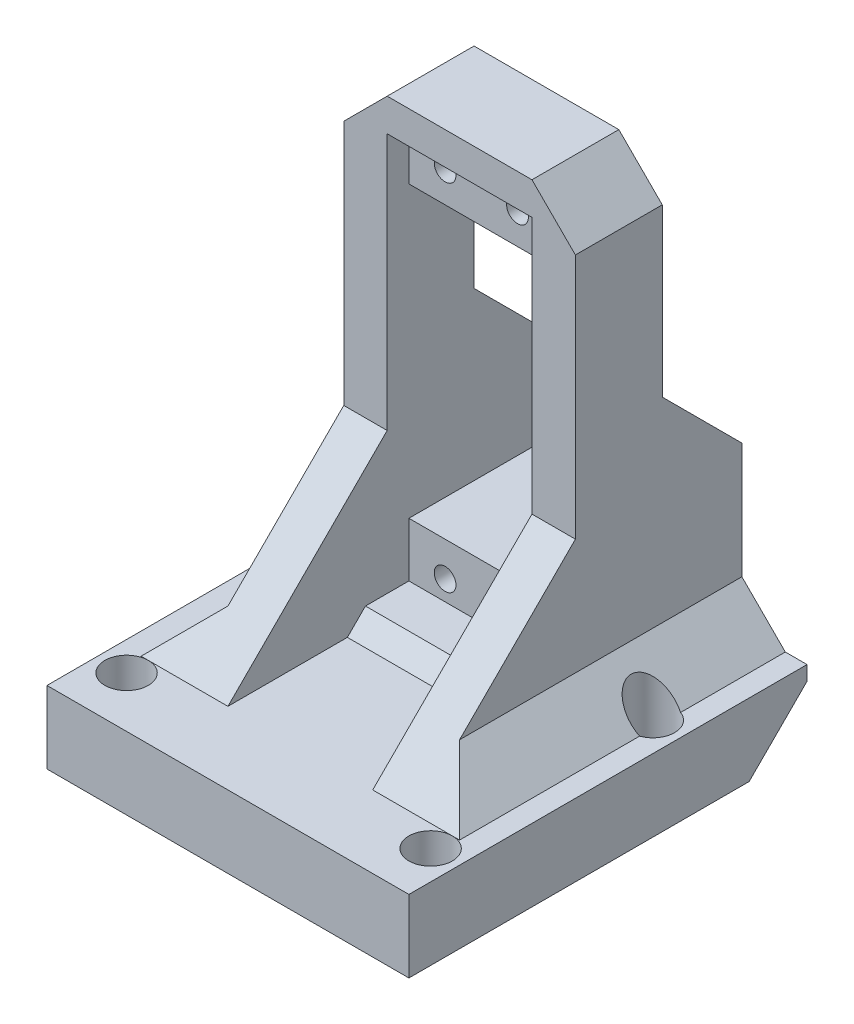
SolidWorks part; units mm, degrees
ref_plane "Front Plane" through (0, 0, 0) normal (0, 0, 1) x (1, 0, 0)
ref_plane "Top Plane" through (0, 0, 0) normal (0, 1, 0) x (1, 0, 0)
ref_plane "Right Plane" through (0, 0, 0) normal (1, 0, 0) x (0, 0, -1)
sketch "Sketch1" plane through (0, 0, 0) normal (0, 1, 0) x (1, 0, 0)
  line L1 (-25, -27.5) -> (25, -27.5)
  line L2 (-25, -27.5) -> (-25, 27.5)
  line L3 (-25, 27.5) -> (25, 27.5)
  line L4 (25, -27.5) -> (25, 27.5)
  line L5 (-25, -27.5) -> (25, 27.5) construction
  line L6 (-25, 27.5) -> (25, -27.5) construction
  point P0 (0, 0)
  dimension "D1" = 50
  dimension "D2" = 55
extrude "Boss-Extrude1" add sketch "Sketch1" along normal blind 10
sketch "Sketch2" plane through (0, 0, 0) normal (0, -1, 0) x (1, 0, 0)
  line L0 (-25, -27.5) -> (-25, 27.5) construction
  line L1 (21, -10.2) -> (-21, -10.2) construction
  line L2 (21, -10.2) -> (21, 20.5) construction
  line L3 (21, 20.5) -> (-21, 20.5) construction
  line L4 (-21, -10.2) -> (-21, 20.5) construction
  line L5 (21, -10.2) -> (-21, 20.5) construction
  line L6 (21, 20.5) -> (-21, -10.2) construction
  line L7 (-25, 27.5) -> (25, 27.5) construction
  line L8 (25, 27.5) -> (25, -27.5) construction
  circle A0 centre (-21, 20.5) radius 1.5
  circle A1 centre (21, 20.5) radius 1.5
  circle A2 centre (21, -10.2) radius 1.5
  circle A3 centre (-21, -10.2) radius 1.5
  point P0 (0, 5.15)
  point P14 (0, 0)
  dimension "D2" = 3
  dimension "D3" = 7
  dimension "D5" = 25
  dimension "D1" = 4
  dimension "D4" = 22.35
extrude "Cut-Extrude1" cut sketch "Sketch2" against normal blind 4
sketch "Sketch3" plane through (0, 4, 0) normal (0, -1, 0) x (1, 0, 0)
  circle A0 centre (-21, 20.5) radius 3
  circle A1 centre (21, 20.5) radius 3
  circle A2 centre (21, -10.2) radius 3
  circle A3 centre (-21, -10.2) radius 3
  dimension "D1" = 6
extrude "Cut-Extrude2" cut sketch "Sketch3" against normal up to next
sketch "Sketch4" plane through (0, 10, 0) normal (0, 1, 0) x (1, 0, 0)
  line L1 (-10, 7.5) -> (10, 7.5)
  line L2 (-10, 7.5) -> (-10, 27.5)
  line L3 (-10, 27.5) -> (10, 27.5)
  line L4 (10, 7.5) -> (10, 27.5)
  line L5 (-10, 7.5) -> (10, 27.5) construction
  line L6 (-10, 27.5) -> (10, 7.5) construction
  line L7 (25, 27.5) -> (-25, 27.5) construction
  point P0 (0, 17.5)
  point P5 (0, 0)
  point P7 (0, 21.2058)
  dimension "D1" = 20
  dimension "D2" = 20
extrude "Boss-Extrude2" add sketch "Sketch4" along normal blind 10
sketch "Sketch5" plane through (10, 0, 0) normal (1, 0, 0) x (0, 0, -1)
  line L1 (-27.5, 10) -> (27.5, 10) construction
  line L2 (-17.5, 10) -> (4.5, 32)
  line L3 (4.5, 32) -> (4.5, 60)
  line L4 (4.5, 60) -> (16.5, 60)
  line L5 (16.5, 60) -> (16.5, 43)
  line L6 (16.5, 43) -> (27.5, 32)
  line L7 (27.5, 32) -> (27.5, 10)
  line L8 (27.5, 10) -> (-17.5, 10)
  line L10 (7.5, 20) -> (27.5, 20) construction
  line L11 (7.5, 20) -> (7.5, 10) construction
  line L12 (-27.5, 10) -> (-27.5, 0) construction
  point P0 (-13.3119, 10)
  point P14 (7.5, 33.1015)
  point P15 (0, 0)
  point P16 (-14.2108, 10)
  point P17 (17.5, 46.9882)
  point P18 (17.5, 53.0949)
  point P21 (0, 0)
  point P22 (0, 0)
  point P23 (-7.5, 10)
  point P24 (-7.5, 10)
  point P25 (-7.5, 10)
  point P26 (-14.0463, 10.1645)
  dimension "D1" = 45
  dimension "D2" = 10
  dimension "D3" = 45
  dimension "D4" = 12
  dimension "D5" = 40
  dimension "D6" = 3
extrude "Boss-Extrude3" add sketch "Sketch5" along normal blind 6
mirror "Mirror1" about plane through (0, 0, 0) normal (1, 0, 0) of "Boss-Extrude3"
sketch "Sketch6" plane through (16, 0, 0) normal (1, 0, 0) x (0, 0, -1)
  line L0 (16.5, 43) -> (16.5, 60) construction
  line L1 (4.5, 60) -> (16.5, 60)
  line L2 (4.5, 60) -> (4.5, 72)
  line L3 (4.5, 72) -> (16.5, 72)
  line L4 (16.5, 60) -> (16.5, 72)
  point P5 (0, 0)
  dimension "D1" = 12
extrude "Boss-Extrude4" add sketch "Sketch6" against normal up to surface (32 mm away) up to face at (-16, 35.2857, -11.3571)
sketch "Sketch7" plane through (0, 0, -7.5) normal (0, 0, 1) x (1, 0, 0)
  line L0 (10, 20) -> (10, 10) construction
  line L1 (-10, 10) -> (10, 10)
  line L2 (-10, 10) -> (-10, 12.5)
  line L3 (-10, 12.5) -> (10, 12.5)
  line L4 (10, 10) -> (10, 12.5)
  dimension "D1" = 2.5
extrude "Boss-Extrude5" add sketch "Sketch7" along normal blind 6
sketch "Sketch8" plane through (0, 0, -4.5) normal (0, 0, 1) x (1, 0, 0)
  line L0 (10, 60) -> (10, 32) construction
  line L1 (-10, 60) -> (10, 60)
  line L2 (-10, 60) -> (-10, 67.5)
  line L3 (-10, 67.5) -> (10, 67.5)
  line L4 (10, 60) -> (10, 67.5)
  point P5 (0, 0)
  dimension "D1" = 7.5
extrude "Cut-Extrude3" cut sketch "Sketch8" against normal blind 3
chamfer "Chamfer1" distance 2.5 angle 45 1 edges at (0, 10, -1.5)
sketch "Sketch9" plane through (0, 0, -7.5) normal (0, 0, 1) x (1, 0, 0)
  line L0 (10, 12.5) -> (-10, 12.5) construction
  line L1 (-5, 15.25) -> (5, 15.25) construction
  line L2 (-5, 15.25) -> (-5, 64.25) construction
  line L3 (-5, 64.25) -> (5, 64.25) construction
  line L4 (5, 15.25) -> (5, 64.25) construction
  line L5 (-5, 15.25) -> (5, 64.25) construction
  line L6 (-5, 64.25) -> (5, 15.25) construction
  circle A0 centre (-5, 64.25) radius 1.5
  circle A1 centre (5, 64.25) radius 1.5
  circle A2 centre (5, 15.25) radius 1.5
  circle A3 centre (-5, 15.25) radius 1.5
  point P0 (0, 39.75)
  point P9 (0, 0)
  point P13 (0, 0)
  dimension "D1" = 3
  dimension "D4" = 2.75
  dimension "D2" = 10
  dimension "D3" = 49
extrude "Cut-Extrude4" cut sketch "Sketch9" against normal up to next
chamfer "Chamfer3" distance 6 angle 45 4 edges at (16, 72, -10.5) (-16, 72, -10.5) (-16, 10, -5) (16, 10, -5)
chamfer "Chamfer4" distance 8 angle 45 1 edges at (0, 0, -27.5)
